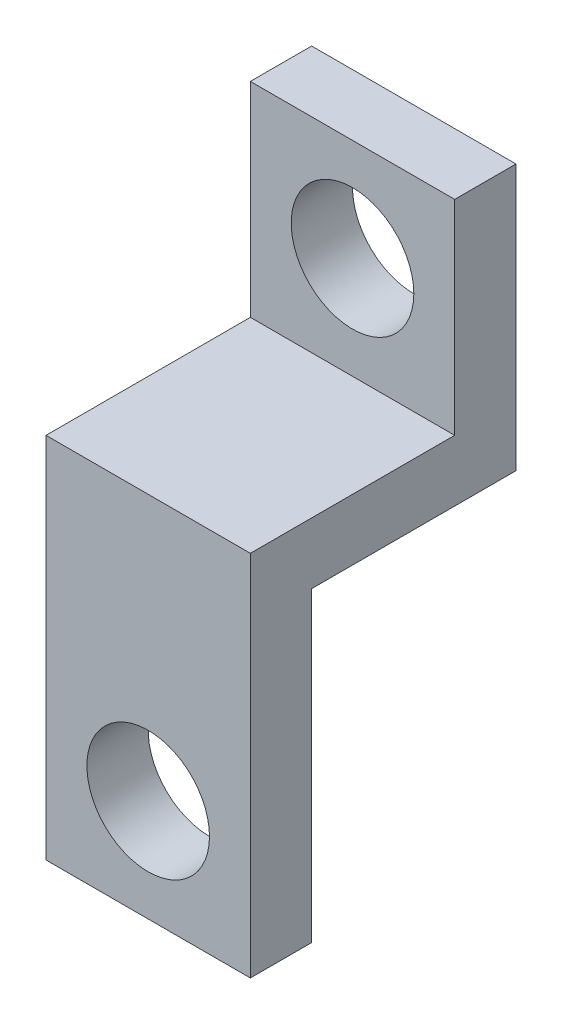
SolidWorks part; units mm, degrees
ref_plane "Front Plane" through (0, 0, 0) normal (0, 0, 1) x (1, 0, 0)
ref_plane "Top Plane" through (0, 0, 0) normal (0, 1, 0) x (1, 0, 0)
ref_plane "Right Plane" through (0, 0, 0) normal (1, 0, 0) x (0, 0, -1)
sketch "Sketch1" plane through (0, 0, 0) normal (0, 0, 1) x (1, 0, 0)
  line L0 (0, 3) -> (10, 3)
  line L1 (0, 0) -> (10, 0)
  line L2 (0, 0) -> (0, -15)
  line L3 (0, -15) -> (10, -15)
  line L4 (10, 0) -> (10, -15)
  line L5 (0, 0) -> (10, 0)
  line L6 (0, 0) -> (0, 13)
  line L7 (0, 13) -> (10, 13)
  line L8 (10, 0) -> (10, 13)
  circle A0 centre (5, -10) radius 3
  circle A1 centre (5, 8) radius 3
  point P11 (0, 0)
  point P12 (5, 13)
  dimension "D4" = 6
  dimension "D1" = 15
  dimension "D2" = 10
  dimension "D3" = 13
  dimension "D5" = 5
  dimension "D6" = 3
  dimension "D7" = 5
extrude "Boss-Extrude1" add sketch "Sketch1" along normal blind 3 contours L4 L1 L2 L3 A0 | L1 L8 L0 L6 region at (5, 1.5, 0) region at (5, -6.9193, 0)
extrude "Boss-Extrude2" add sketch "Sketch1<4>" against normal blind 10 contours L1 L8 L0 L6 region at (5, 1.5, 0)
sketch "Sketch1<4>" plane through (0, 0, 0) normal (0, 0, 1) x (1, 0, 0) same geometry as "Sketch1"
extrude "Boss-Extrude3" add sketch "Sketch1<5>" along normal blind 3 from surface contours L0 L8 L7 L6 A1 region at (0.1414, 8, 0) starting at face at (5, 1.5, -10)
sketch "Sketch1<5>" plane through (0, 0, 0) normal (0, 0, 1) x (1, 0, 0) same geometry as "Sketch1"
